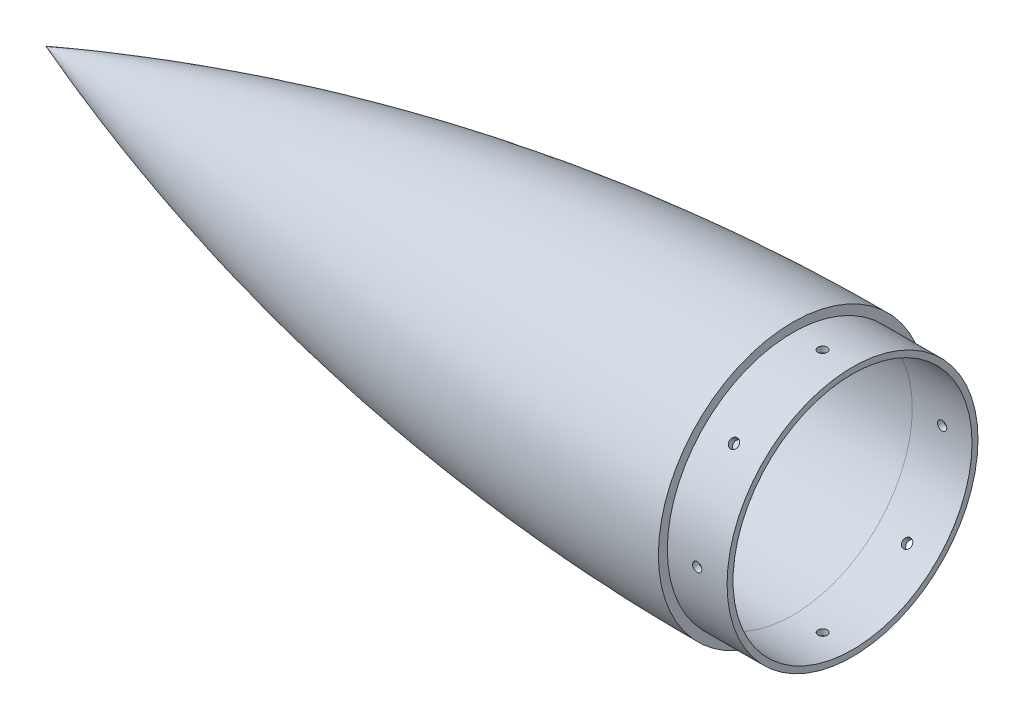
SolidWorks part; units mm, degrees
material "Alliage 1060"
ref_plane "Plan de face" through (0, 0, 0) normal (0, 0, 1) x (1, 0, 0)
ref_plane "Plan de dessus" through (0, 0, 0) normal (0, 1, 0) x (1, 0, 0)
ref_plane "Plan de droite" through (0, 0, 0) normal (1, 0, 0) x (0, 0, -1)
sketch "Esquisse1" plane through (0, 0, 0) normal (0, 1, 0) x (1, 0, 0)
  line L0 (0, 0) -> (301.6119, 0) construction
  line L1 (250, 45) -> (250, 0)
  line L2 (250, 0) -> (0, 0) construction
  line L3 (250, 0) -> (0, 0)
  line L4 (-54.2063, 0) -> (320.9698, 0) construction
  spline S0 degree 4 poles (-23.75, -9.3206) (-23.3793, -9.1675) (-22.6378, -8.8618) (-21.1533, -8.2524) (-18.9254, -7.3456) (-16.3195, -6.2962) (-13.3492, -5.1155) (-10.3763, -3.9492) (-7.7868, -2.9463) (-5.5576, -2.0927) (-3.7137, -1.3926) (-2.2648, -0.8461) (-0.1075, -0.0388) (0.8923, 0.3317) (3.5178, 1.3014) (4.8595, 1.7876) (6.481, 2.3772) (7.8299, 2.8619) (9.2895, 3.3843) (11.7855, 4.2708) (14.6616, 5.279) (17.8907, 6.3927) (22.2119, 7.856) (26.5382, 9.2938) (31.5993, 10.9361) (37.3979, 12.7636) (43.2125, 14.542) (49.0415, 16.271) (56.3462, 18.3703) (65.1397, 20.7903) (73.9667, 23.0858) (82.8251, 25.2563) (90.227, 26.9814) (96.16, 28.3112) (103.5901, 29.9105) (112.5275, 31.7288) (121.4898, 33.4206) (130.475, 34.9856) (139.4772, 36.4488) (148.4954, 37.8102) (157.5322, 39.0439) (166.5854, 40.1499) (174.1395, 40.9861) (180.1882, 41.6038) (186.242, 42.1702) (192.3004, 42.6852) (197.6051, 43.0908) (202.1542, 43.4064) (205.9467, 43.648) (208.9814, 43.8283) (212.0168, 43.9958) (215.053, 44.1504) (218.0897, 44.2922) (221.1271, 44.4211) (224.165, 44.5371) (227.2032, 44.6402) (230.242, 44.7304) (233.281, 44.8077) (235.9407, 44.8641) (238.2201, 44.9044) (240.1205, 44.9326) (241.6389, 44.9519) (243.1631, 44.968) (244.6703, 44.9809) (246.2317, 44.9906) (247.6173, 44.997) (249.5342, 45.0003) (250.4911, 45.0003) (252.4435, 44.9969) (253.8441, 44.9902) (255.4491, 44.9801) (256.9849, 44.9666) (258.9327, 44.9456) (261.2684, 44.9135) (264.0075, 44.866) (267.1406, 44.7979) (269.8924, 44.7261) (272.2495, 44.6559) (273.8214, 44.6045) (274.6071, 44.5777) (275, 44.564) knots 0 0 0 0 0 0.005245 0.010489 0.020979 0.031468 0.041958 0.052322 0.062685 0.067867 0.073049 0.078231 0.083413 0.093352 0.098321 0.10329 0.108259 0.113229 0.118198 0.123167 0.143044 0.152983 0.162922 0.182799 0.202676 0.222553 0.24243 0.262307 0.282185 0.321939 0.361693 0.38157 0.401447 0.421325 0.441202 0.480956 0.52071 0.540588 0.560465 0.600219 0.639973 0.65985 0.679728 0.699605 0.719482 0.739359 0.759236 0.769175 0.779113 0.789052 0.798991 0.808929 0.818868 0.828806 0.838745 0.848683 0.858622 0.868561 0.878499 0.883468 0.888438 0.893407 0.898376 0.903346 0.908315 0.913284 0.918253 0.923331 0.928409 0.933486 0.938564 0.943642 0.948719 0.958874 0.969156 0.979437 0.989719 0.994859 1 1 1 1 1 construction
  spline S1 degree 4 poles (0, 0) (0.5947, 0.2212) (1.4352, 0.5323) (3.5178, 1.3014) (4.8595, 1.7876) (6.481, 2.3772) (7.8299, 2.8619) (9.2895, 3.3843) (11.7855, 4.2708) (14.6616, 5.279) (17.8907, 6.3927) (22.2119, 7.856) (26.5382, 9.2938) (31.5993, 10.9361) (37.3979, 12.7636) (43.2125, 14.542) (49.0415, 16.271) (56.3462, 18.3703) (65.1397, 20.7903) (73.9667, 23.0858) (82.8251, 25.2563) (90.227, 26.9814) (96.16, 28.3112) (103.5901, 29.9105) (112.5275, 31.7288) (121.4898, 33.4206) (130.475, 34.9856) (139.4772, 36.4488) (148.4954, 37.8102) (157.5322, 39.0439) (166.5854, 40.1499) (174.1395, 40.9861) (180.1882, 41.6038) (186.242, 42.1702) (192.3004, 42.6852) (197.6051, 43.0908) (202.1542, 43.4064) (205.9467, 43.648) (208.9814, 43.8283) (212.0168, 43.9958) (215.053, 44.1504) (218.0897, 44.2922) (221.1271, 44.4211) (224.165, 44.5371) (227.2032, 44.6402) (230.242, 44.7304) (233.281, 44.8077) (235.9407, 44.8641) (238.2201, 44.9044) (240.1205, 44.9326) (241.6389, 44.9519) (243.1631, 44.968) (244.6703, 44.9809) (246.2317, 44.9906) (247.6173, 44.997) (249.0472, 44.9995) (249.6828, 45) (250, 45) knots 0.083413 0.083413 0.083413 0.083413 0.083413 0.093352 0.098321 0.10329 0.108259 0.113229 0.118198 0.123167 0.143044 0.152983 0.162922 0.182799 0.202676 0.222553 0.24243 0.262307 0.282185 0.321939 0.361693 0.38157 0.401447 0.421325 0.441202 0.480956 0.52071 0.540588 0.560465 0.600219 0.639973 0.65985 0.679728 0.699605 0.719482 0.739359 0.759236 0.769175 0.779113 0.789052 0.798991 0.808929 0.818868 0.828806 0.838745 0.848683 0.858622 0.868561 0.878499 0.883468 0.888438 0.893407 0.898376 0.903346 0.908315 0.913284 0.918253 0.918253 0.918253 0.918253 0.918253
  dimension "D1" = 250
  dimension "D2" = 45
revolve "Révolution1" add sketch "Esquisse1" angle 360 about L3
shell "Coque4" thickness 5 removed face at (250, 0, -45)
sketch "Esquisse2" plane through (250, 0, 0) normal (1, 0, 0) x (0, 0, -1)
sketch "Esquisse3" plane through (250, 0, 0) normal (1, 0, 0) x (0, 0, -1)
  circle A0 centre (0, 0) radius 40
  circle A1 centre (0, 0) radius 42
  dimension "D1" = 84
  dimension "D2" = 80
extrude "Boss.-Extru.1" add sketch "Esquisse3" along normal blind 20
hole_wizard "Dégagement M2.51" positions "Esquisse3D1" profile "Esquisse4" hole size "M2.5" standard "ISO" end condition through all
sketch3d "Esquisse3D1"
  line L0 (270, 0, -0.2361) -> (270, 0, -70.2522) construction
  line L2 (270, 0, -42) -> (253.0975, 0, -42) construction
  point P0 (260, 0, -42)
  dimension "D1" = 10
sketch "Esquisse4" plane through (260, 0, -42) normal (1, 0, 0) x (0, 1, 0)
  line L0 (0, 0) -> (0, 105.6396)
  line L1 (0, 105.6396) -> (1.55, 105.6396)
  line L2 (1.55, 105.6396) -> (1.55, 0)
  line L5 (1.55, 0) -> (0, 0)
  line L11 (0, -6.35) -> (0, 107.95) construction
  dimension "Diamètre du perçage jusqu'au prochain" = 3.1
  dimension "Profondeur du perçage jusqu'au prochain" = 105.6396
pattern_circular "Répétition circulaire1" count 8 over 360 about axis through (270, 0, 0) along (1, 0, 0) of "Dégagement M2.51"
